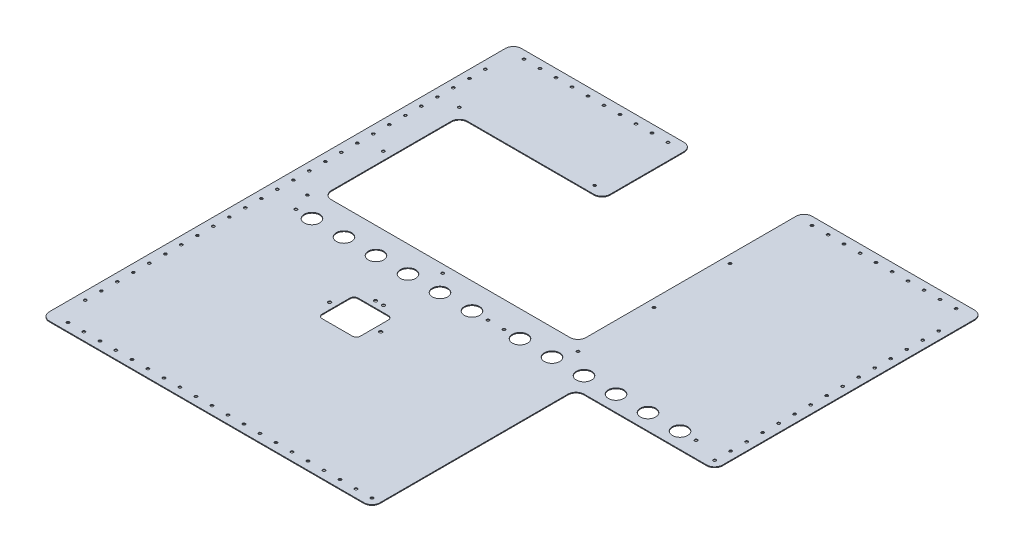
SolidWorks part; units mm, degrees
material "3003-H12"
ref_plane "Front Plane" through (0, 0, 0) normal (0, 0, 1) x (1, 0, 0)
ref_plane "Top Plane" through (0, 0, 0) normal (0, 1, 0) x (1, 0, 0)
ref_plane "Right Plane" through (0, 0, 0) normal (1, 0, 0) x (0, 0, -1)
sketch "Sketch1" plane through (0, 0, 0) normal (0, 1, 0) x (1, 0, 0)
  line L1 (-293.265, 295) -> (293.265, 295)
  line L2 (-293.265, 295) -> (-293.265, -295)
  line L3 (-293.265, -295) -> (293.265, -295)
  line L4 (293.265, 295) -> (293.265, -295)
  line L5 (-293.265, 295) -> (293.265, -295) construction
  line L6 (-293.265, -295) -> (293.265, 295) construction
  point P0 (0, 0)
  dimension "D1" = 590
  dimension "D2" = 586.53
base flange "Base-Flange1" sketch "Sketch1" thickness 1 reverse thickness direction no parameters "D1"=0.5
sketch "Sketch6" plane through (0, 0, 0) normal (0, 1, 0) x (1, 0, 0)
  line L0 (-293.265, 295) -> (-293.265, -295) construction
  line L1 (293.265, -295) -> (119.995, -295)
  line L2 (293.265, -295) -> (293.265, -40)
  line L3 (293.265, -40) -> (119.995, -40)
  line L4 (119.995, -295) -> (119.995, -40)
  line L5 (-248.265, 182.5) -> (70.005, 182.5)
  line L6 (-248.265, 182.5) -> (-248.265, 12.5)
  line L7 (-248.265, 12.5) -> (70.005, 12.5)
  line L8 (70.005, 182.5) -> (70.005, 12.5)
  line L9 (-248.265, 182.5) -> (70.005, 12.5) construction
  line L10 (-248.265, 12.5) -> (70.005, 182.5) construction
  line L11 (-293.265, 295) -> (293.265, 295) construction
  point P5 (-89.13, 97.5)
  dimension "D1" = 45
  dimension "D2" = 112.5
  dimension "D3" = 255
  dimension "D4" = 173.27
  dimension "D5" = 318.27
  dimension "D6" = 170
extrude "Cut-Extrude1" cut sketch "Sketch6" against normal blind 10 normal cut yes
sketch "Sketch9" plane through (0, 0, 0) normal (0, 1, 0) x (1, 0, 0)
  line L0 (-293.265, 295) -> (293.265, 295) construction
  line L1 (-70, 295) -> (70, 295)
  line L2 (-70, 295) -> (-70, 182.49)
  line L3 (-70, 182.49) -> (70, 182.49)
  line L4 (70, 295) -> (70, 182.49)
  line L5 (0, 182.49) -> (0, 0) construction
  dimension "D1" = 112.51
  dimension "D2" = 140
extrude "Cut-Extrude2" cut sketch "Sketch9" against normal blind 10 normal cut yes
fillet "Fillet1" radius 10 12 edges at (-293.265, -0.5, 295) (-293.265, -0.5, -295) (293.265, -0.5, -295) (293.265, -0.5, 40) (119.995, -0.5, 40) (119.995, -0.5, 295) (-70, -0.5, -295) (70, -0.5, -295) (70.005, -0.5, -12.5) (-70, -0.5, -182.5) (-248.265, -0.5, -182.5) (-248.265, -0.5, -12.5)
hole_wizard "M3 Clearance Hole1" positions "Sketch10" profile "Sketch11" hole size "M3" standard "ANSI Metric" end condition through all
sketch "Sketch10" plane through (0, 0, 0) normal (0, 1, 0) x (1, 0, 0)
  line L10 (-258.265, 2.5) -> (80.005, 2.5)
  line L11 (-258.265, 2.5) -> (-258.265, 192.5)
  line L12 (-258.265, 192.5) -> (80.005, 192.5)
  line L13 (80.005, 2.5) -> (80.005, 192.5)
  line L14 (-80, 182.5) -> (-238.265, 182.5) construction
  line L15 (-248.265, 172.5) -> (-248.265, 22.5) construction
  line L16 (-238.265, 12.5) -> (60.005, 12.5) construction
  line L17 (70.005, 22.5) -> (70.005, 182.5) construction
  point P195 (-89.13, 192.5)
  point P199 (-258.265, 192.5)
  point P200 (-258.265, 97.5)
  point P204 (-258.265, 2.5)
  point P205 (-89.13, 2.5)
  point P209 (80.005, 2.5)
  point P210 (80.005, 97.5)
  point P214 (80.005, 192.5)
  dimension "D4" = 10
  dimension "D5" = 10
  dimension "D6" = 10
  dimension "D7" = 10
sketch "Sketch11" plane through (80.005, 0, -192.5) normal (1, 0, 0) x (0, 0, 1)
  line L0 (0, 0) -> (0, 1)
  line L1 (0, 1) -> (1.7, 1)
  line L2 (1.7, 1) -> (1.7, 0.025)
  line L3 (1.7, 0.025) -> (1.725, 0)
  line L5 (1.725, 0) -> (0, 0)
  line L6 (-1.7, 0.025) -> (-1.725, 0) construction
  line L11 (0, -6.35) -> (0, 107.95) construction
  dimension "Thru Hole Dia." = 3.4
  dimension "Thru Hole Depth" = 1
  dimension "Near C'Sink Dia." = 3.45
  dimension "Near C'Sink Angle" = 90
hole_wizard "M3 Clearance Hole2" positions "Sketch12" profile "Sketch13" hole size "M3" standard "ANSI Metric" end condition through all
sketch "Sketch12" plane through (0, 0, 0) normal (0, 1, 0) x (1, 0, 0)
  line L0 (-293.265, 285) -> (-293.265, -285) construction
  line L1 (-283.265, -295) -> (109.995, -295) construction
  line L2 (283.265, 295) -> (80, 295) construction
  line L3 (293.265, -30) -> (293.265, 285) construction
  line L4 (-80, 295) -> (-283.265, 295) construction
  point P0 (-270.005, -285)
  point P13 (-250.005, -285)
  point P14 (-230.005, -285)
  point P15 (-210.005, -285)
  point P16 (-190.005, -285)
  point P17 (-170.005, -285)
  point P18 (-150.005, -285)
  point P19 (-130.005, -285)
  point P20 (-110.005, -285)
  point P21 (-90.005, -285)
  point P22 (-70.005, -285)
  point P23 (-50.005, -285)
  point P24 (-30.005, -285)
  point P25 (-10.005, -285)
  point P26 (9.995, -285)
  point P27 (29.995, -285)
  point P28 (49.995, -285)
  point P29 (69.995, -285)
  point P30 (89.995, -285)
  point P31 (109.995, -285)
  point P32 (-283.265, -250)
  point P46 (-283.265, -230)
  point P47 (-283.265, -210)
  point P48 (-283.265, -190)
  point P49 (-283.265, -170)
  point P50 (-283.265, -150)
  point P51 (-283.265, -130)
  point P52 (-283.265, -110)
  point P53 (-283.265, -90)
  point P54 (-283.265, -70)
  point P55 (-283.265, -50)
  point P56 (-283.265, -30)
  point P57 (-283.265, -10)
  point P58 (-283.265, 10)
  point P59 (-283.265, 30)
  point P60 (-283.265, 50)
  point P61 (-283.265, 70)
  point P62 (-283.265, 90)
  point P63 (-283.265, 110)
  point P64 (-283.265, 130)
  point P65 (-283.265, 150)
  point P66 (-283.265, 170)
  point P67 (-283.265, 190)
  point P68 (-283.265, 210)
  point P69 (-283.265, 230)
  point P70 (-283.265, 250)
  point P71 (283.265, 250)
  point P84 (283.265, 230)
  point P85 (283.265, 210)
  point P86 (283.265, 190)
  point P87 (283.265, 170)
  point P88 (283.265, 150)
  point P89 (283.265, 130)
  point P90 (283.265, 110)
  point P91 (283.265, 90)
  point P92 (283.265, 70)
  point P93 (283.265, 50)
  point P94 (283.265, 30)
  point P95 (283.265, 10)
  point P96 (283.265, -10)
  point P97 (283.265, -30)
  point P98 (-270.005, 285)
  point P108 (-250.005, 285)
  point P109 (-230.005, 285)
  point P110 (-210.005, 285)
  point P111 (-190.005, 285)
  point P112 (-170.005, 285)
  point P113 (-150.005, 285)
  point P114 (-130.005, 285)
  point P115 (-110.005, 285)
  point P116 (-90.005, 285)
  point P117 (270.005, 285)
  point P124 (250.005, 285)
  point P125 (230.005, 285)
  point P126 (210.005, 285)
  point P127 (190.005, 285)
  point P128 (170.005, 285)
  point P129 (150.005, 285)
  point P130 (130.005, 285)
  point P131 (110.005, 285)
  point P132 (90.005, 285)
  dimension "D1" = 23.26
  dimension "D2" = 10
  dimension "D4" = 20
  dimension "D5" = 45
  dimension "D6" = 10
  dimension "D8" = 20
  dimension "D9" = 45
  dimension "D10" = 10
  dimension "D12" = 20
  dimension "D13" = 23.26
  dimension "D14" = 10
  dimension "D16" = 20
  dimension "D17" = 23.26
  dimension "D18" = 10
  dimension "D20" = 20
  dimension "D3" = 20
  dimension "D7" = 26
  dimension "D11" = 15
  dimension "D15" = 10
  dimension "D19" = 10
sketch "Sketch13" plane through (-270.005, 0, 285) normal (1, 0, 0) x (0, 0, 1)
  line L0 (0, 0) -> (0, 1)
  line L1 (0, 1) -> (1.7, 1)
  line L2 (1.7, 1) -> (1.7, 0.025)
  line L3 (1.7, 0.025) -> (1.725, 0)
  line L5 (1.725, 0) -> (0, 0)
  line L6 (-1.7, 0.025) -> (-1.725, 0) construction
  line L11 (0, -6.35) -> (0, 107.95) construction
  dimension "Thru Hole Dia." = 3.4
  dimension "Thru Hole Depth" = 1
  dimension "Near C'Sink Dia." = 3.45
  dimension "Near C'Sink Angle" = 90
sketch "Sketch14" plane through (0, 0, 0) normal (0, 1, 0) x (1, 0, 0)
  line L0 (-30, -20) -> (0, -20) construction
  line L3 (0, -20) -> (0, 0) construction
  circle A0 centre (-230, -20) radius 9.55
  circle A1 centre (-190, -20) radius 9.55
  circle A2 centre (-150, -20) radius 9.55
  circle A3 centre (-110, -20) radius 9.55
  circle A4 centre (-70, -20) radius 9.55
  circle A5 centre (-30, -20) radius 9.55
  circle A12 centre (230, -20) radius 9.55
  circle A13 centre (190, -20) radius 9.55
  circle A14 centre (150, -20) radius 9.55
  circle A15 centre (110, -20) radius 9.55
  circle A16 centre (70, -20) radius 9.55
  circle A17 centre (30, -20) radius 9.55
  dimension "D4" = 19.1
  dimension "D2" = 40
  dimension "D3" = 30
  dimension "D5" = 20
  dimension "D1" = 6
extrude "Cut-Extrude3" cut sketch "Sketch14" against normal blind 10 normal cut yes
sketch "Sketch15" plane through (0, 0, 0) normal (0, 1, 0) x (1, 0, 0)
  line L4 (-120.265, -82.2) -> (-120.265, -117)
  line L5 (-115.265, -122) -> (-77.465, -122)
  line L6 (-72.465, -117) -> (-72.465, -82.2)
  line L7 (-77.465, -77.2) -> (-115.265, -77.2)
  line L8 (-120.265, -82.2) -> (-120.265, -117)
  line L9 (-115.265, -122) -> (-77.465, -122)
  line L10 (-72.465, -117) -> (-72.465, -82.2)
  line L11 (-77.465, -77.2) -> (-115.265, -77.2)
  circle A1 centre (-91.365, -69.2) radius 1.95
  circle A2 centre (-91.365, -69.2) radius 1.95
  circle A3 centre (-101.365, -69.2) radius 1.95
  circle A4 centre (-101.365, -69.2) radius 1.95
  circle A5 centre (-64.465, -99.6) radius 1.95
  circle A6 centre (-64.465, -99.6) radius 1.95
  circle A7 centre (-128.265, -99.6) radius 1.95
  circle A8 centre (-128.265, -99.6) radius 1.95
  arc A12 (-120.265, -117) -> (-115.265, -122) centre (-115.265, -117) ccw
  arc A13 (-77.465, -122) -> (-72.465, -117) centre (-77.465, -117) ccw
  arc A14 (-72.465, -82.2) -> (-77.465, -77.2) centre (-77.465, -82.2) ccw
  arc A15 (-115.265, -77.2) -> (-120.265, -82.2) centre (-115.265, -82.2) ccw
  arc A16 (-120.265, -117) -> (-115.265, -122) centre (-115.265, -117) ccw
  arc A17 (-77.465, -122) -> (-72.465, -117) centre (-77.465, -117) ccw
  arc A18 (-72.465, -82.2) -> (-77.465, -77.2) centre (-77.465, -82.2) ccw
  arc A19 (-115.265, -77.2) -> (-120.265, -82.2) centre (-115.265, -82.2) ccw
  dimension "D1" = 0
  dimension "D2" = 0
  dimension "D3" = 0
  dimension "D4" = 0
  dimension "D5" = 0
extrude "Cut-Extrude5" cut sketch "Sketch15" against normal through all normal cut yes
sketch "Sketch16" plane through (0, 0, 0) normal (0, 1, 0) x (1, 0, 0)
  line L0 (-250, -20) -> (0, -20) construction
  line L1 (0, -20) -> (250, -20) construction
  line L2 (-10, -20) -> (10, -20) construction
  circle A0 centre (-250, -20) radius 1.75
  circle A1 centre (250, -20) radius 1.75
  circle A3 centre (-10, -20) radius 1.75
  circle A4 centre (10, -20) radius 1.75
  point P4 (-110, -20)
  point P12 (0, -20)
  dimension "D1" = 3.5
  dimension "D2" = 20
  dimension "D3" = 250
extrude "Cut-Extrude6" cut sketch "Sketch16" against normal through all normal cut yes
sketch "Bend-Lines1" [suppressed] plane through (0, 0, 0) normal (0, 1, 0) x (1, 0, 0)
sketch "Bounding-Box1" [suppressed] plane through (0, 0, 0) normal (0, 1, 0) x (1, 0, 0)
sheet metal parameters "Sheet-Metal1" thickness 1 parameters "D1"=0.5
flat pattern "Flat-Pattern1" [suppressed]
sketch "Bend-Lines2" plane through (0, 0, 0) normal (0, 1, 0) x (1, 0, 0)
sketch3d "Bounding-Box2" [suppressed]
  line L0 (293.265, 295, 0) -> (293.265, -295, 0) construction
  line L1 (-293.265, 295, 0) -> (-293.265, -295, 0) construction
  line L2 (293.265, 295, 0) -> (-293.265, 295, 0) construction
  line L3 (293.265, -295, 0) -> (-293.265, -295, 0) construction
sheet metal parameters "Sheet-Metal2" thickness 1 parameters "D1"=0.5
flat pattern "Flat-Pattern1"
sketch "Bend-Lines2" plane through (0, 0, 0) normal (0, 1, 0) x (1, 0, 0)
sketch3d "Bounding-Box2" [suppressed]
  line L0 (293.265, 295, 0) -> (293.265, -295, 0) construction
  line L1 (-293.265, 295, 0) -> (-293.265, -295, 0) construction
  line L2 (293.265, 295, 0) -> (-293.265, 295, 0) construction
  line L3 (293.265, -295, 0) -> (-293.265, -295, 0) construction
sheet metal parameters "Sheet-Metal3" thickness 1 parameters "D1"=0.5
flat pattern "Flat-Pattern1"
sketch "Bend-Lines2" plane through (0, 0, 0) normal (0, 1, 0) x (1, 0, 0)
sketch3d "Bounding-Box2" [suppressed]
  line L0 (293.265, 295, 0) -> (293.265, -295, 0) construction
  line L1 (-293.265, 295, 0) -> (-293.265, -295, 0) construction
  line L2 (293.265, 295, 0) -> (-293.265, 295, 0) construction
  line L3 (293.265, -295, 0) -> (-293.265, -295, 0) construction
sheet metal parameters "Sheet-Metal6" thickness 1 parameters "D1"=0.5
flat pattern "Flat-Pattern1"
sketch "Bend-Lines2" plane through (0, 0, 0) normal (0, 1, 0) x (1, 0, 0)
sketch3d "Bounding-Box2" [suppressed]
  line L0 (293.265, 295, -1) -> (293.265, -295, -1) construction
  line L1 (-293.265, 295, -1) -> (-293.265, -295, -1) construction
  line L2 (293.265, 295, -1) -> (-293.265, 295, -1) construction
  line L3 (293.265, -295, -1) -> (-293.265, -295, -1) construction
sheet metal parameters "Sheet-Metal7" thickness 1 parameters "D1"=0.5
flat pattern "Flat-Pattern1"
sketch "Bend-Lines2" plane through (0, 0, 0) normal (0, 1, 0) x (1, 0, 0)
sketch3d "Bounding-Box2" [suppressed]
  line L0 (293.265, 295, -1) -> (293.265, -295, -1) construction
  line L1 (-293.265, 295, -1) -> (-293.265, -295, -1) construction
  line L2 (293.265, 295, -1) -> (-293.265, 295, -1) construction
  line L3 (293.265, -295, -1) -> (-293.265, -295, -1) construction
sheet metal parameters "Sheet-Metal8" thickness 1 parameters "D1"=0.5
flat pattern "Flat-Pattern1"
sketch "Bend-Lines2" plane through (0, 0, 0) normal (0, 1, 0) x (1, 0, 0)
sketch3d "Bounding-Box2" [suppressed]
  line L0 (293.265, 295, -1) -> (293.265, -295, -1) construction
  line L1 (-293.265, 295, -1) -> (-293.265, -295, -1) construction
  line L2 (293.265, 295, -1) -> (-293.265, 295, -1) construction
  line L3 (293.265, -295, -1) -> (-293.265, -295, -1) construction
sheet metal parameters "Sheet-Metal9" thickness 1 parameters "D1"=0.5
flat pattern "Flat-Pattern1"
sketch "Bend-Lines2" plane through (0, 0, 0) normal (0, 1, 0) x (1, 0, 0)
sketch3d "Bounding-Box2" [suppressed]
  line L0 (293.265, 295, -1) -> (293.265, -295, -1) construction
  line L1 (-293.265, 295, -1) -> (-293.265, -295, -1) construction
  line L2 (293.265, 295, -1) -> (-293.265, 295, -1) construction
  line L3 (293.265, -295, -1) -> (-293.265, -295, -1) construction
sheet metal parameters "Sheet-Metal10" thickness 1 parameters "D1"=0.5
flat pattern "Flat-Pattern1"
sketch "Bend-Lines2" plane through (0, 0, 0) normal (0, 1, 0) x (1, 0, 0)
sketch3d "Bounding-Box2" [suppressed]
  line L0 (293.265, 295, -1) -> (293.265, -295, -1) construction
  line L1 (-293.265, 295, -1) -> (-293.265, -295, -1) construction
  line L2 (293.265, 295, -1) -> (-293.265, 295, -1) construction
  line L3 (293.265, -295, -1) -> (-293.265, -295, -1) construction
